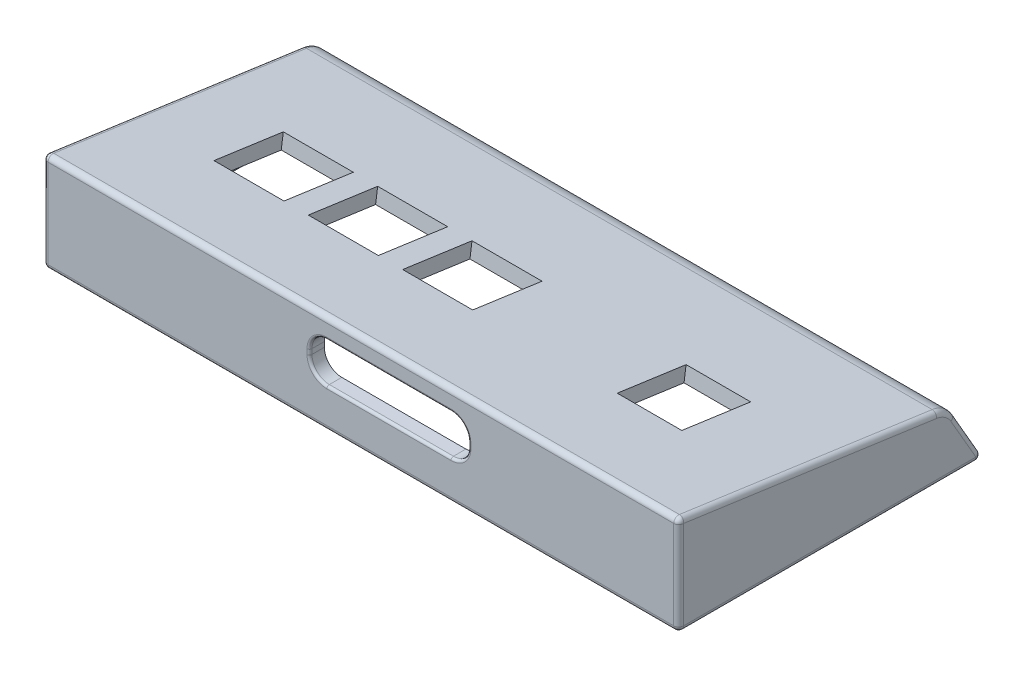
SolidWorks part; units mm, degrees
ref_plane "前视基准面" through (0, 0, 0) normal (0, 0, 1) x (1, 0, 0)
ref_plane "上视基准面" through (0, 0, 0) normal (0, 1, 0) x (1, 0, 0)
ref_plane "右视基准面" through (0, 0, 0) normal (1, 0, 0) x (0, 0, -1)
other "Configuration Table"
sketch "草图1" plane through (0, 0, 0) normal (1, 0, 0) x (0, 0, -1)
  line L0 (0, 0) -> (3, 0)
  line L1 (61.5924, 0) -> (54.4647, 12.3455)
  line L2 (54.4647, 12.3455) -> (0, 20)
  line L3 (0, 20) -> (0, 0)
  line L5 (58.1283, 0) -> (52.5983, 9.5783)
  line L6 (52.5983, 9.5783) -> (3, 16.5489)
  line L7 (3, 16.5489) -> (3, 0)
  line L8 (3, 16.5489) -> (3, 3) construction
  line L9 (56.3963, 3) -> (52.5983, 9.5783) construction
  line L10 (58.1283, 0) -> (61.5924, 0)
  line L11 (0, 0) -> (61.5924, 0) construction
  line L12 (3, 3) -> (56.3963, 3) construction
  dimension "D1" = 55
  dimension "D2" = 3
  dimension "D3" = 20
extrude "凸台-拉伸1" add sketch "草图1" along normal blind 125
sketch "草图2" plane through (0, 19.6126, -2.7564) normal (0, 0.9903, -0.1392) x (1, 0, 0)
  line L1 (97.149, 29.8765) -> (110.149, 29.8765)
  line L2 (97.149, 29.8765) -> (97.149, 15.8765)
  line L3 (97.149, 15.8765) -> (110.149, 15.8765)
  line L4 (110.149, 29.8765) -> (110.149, 15.8765)
  line L5 (53.988, 29.9265) -> (68.088, 29.9265)
  line L6 (53.988, 29.9265) -> (53.988, 15.8265)
  line L7 (53.988, 15.8265) -> (68.088, 15.8265)
  line L8 (68.088, 29.9265) -> (68.088, 15.8265)
  line L18 (62.5, 41.0069) -> (62.5, -31.3643) construction
  line L19 (125, 52.2165) -> (125, -2.7835) construction
  line L20 (34.988, 29.9265) -> (49.088, 29.9265)
  line L21 (34.988, 29.9265) -> (34.988, 15.8265)
  line L22 (34.988, 15.8265) -> (49.088, 15.8265)
  line L23 (49.088, 29.9265) -> (49.088, 15.8265)
  line L24 (15.988, 29.9265) -> (30.088, 29.9265)
  line L25 (15.988, 29.9265) -> (15.988, 15.8265)
  line L26 (15.988, 15.8265) -> (30.088, 15.8265)
  line L27 (30.088, 29.9265) -> (30.088, 15.8265)
  line L31 (-5.112, 22.8765) -> (145.7545, 22.8765) construction
  line L32 (125, -2.7835) -> (0, -2.7835) construction
  dimension "D1" = 13
  dimension "D2" = 14
  dimension "D3" = 14.1
  dimension "D4" = 14.1
  dimension "D5" = 7.05
  dimension "D7" = 62.5
  dimension "D8" = 7
  dimension "D9" = 34.649
  dimension "D10" = 3
  dimension "D6" = 8.512
  dimension "D11" = 25.66
extrude "切除-拉伸1" cut sketch "草图2" against normal blind 5
sketch "草图4" plane through (0, 0, 0) normal (0, 0, 1) x (1, 0, 0)
  line L0 (125, 20) -> (0, 20) construction
  line L1 (53.649, 15.9) -> (85.649, 15.9)
  line L2 (53.649, 15.9) -> (53.649, 7.9)
  line L3 (53.649, 7.9) -> (85.649, 7.9)
  line L4 (85.649, 15.9) -> (85.649, 7.9)
  line L5 (62.5, 49.94) -> (62.5, 4.3344) construction
  dimension "D1" = 4.1
  dimension "D2" = 23.149
  dimension "D3" = 8.851
  dimension "D4" = 8
extrude "切除-拉伸2" cut sketch "草图4" against normal blind 3
fillet "圆角2" radius 3.5 4 edges at (53.649, 7.9, -1.5) (53.649, 15.9, -1.5) (85.649, 7.9, -1.5) (85.649, 15.9, -1.5)
sketch "草图5" plane through (0, 0, 0) normal (-1, 0, 0) x (0, 0, 1)
  line L0 (-58.1283, 0) -> (-3, 0)
  line L8 (0, 0) -> (0, 20)
  line L9 (0, 20) -> (-54.4647, 12.3455)
  line L10 (-54.4647, 12.3455) -> (-61.5924, 0)
  line L11 (-61.5924, 0) -> (-58.1283, 0)
  line L12 (-58.1283, 0) -> (-52.5983, 9.5783)
  line L13 (-52.5983, 9.5783) -> (-3, 16.5489)
  line L14 (-3, 16.5489) -> (-3, 0)
  line L15 (-3, 0) -> (0, 0)
  line L16 (0, 0) -> (0, 20)
  line L17 (0, 20) -> (-54.4647, 12.3455)
  line L18 (-54.4647, 12.3455) -> (-61.5924, 0)
  line L19 (-61.5924, 0) -> (-58.1283, 0)
  line L23 (-3, 0) -> (0, 0)
  dimension "D1" = 0
extrude "凸台-拉伸2" add sketch "草图5" against normal blind 3
sketch "草图6" plane through (125, 0, 0) normal (1, 0, 0) x (0, 0, -1)
  line L0 (3, 0) -> (58.1283, 0)
  line L8 (0, 20) -> (0, 0)
  line L9 (0, 0) -> (3, 0)
  line L10 (3, 0) -> (3, 16.5489)
  line L11 (3, 16.5489) -> (52.5983, 9.5783)
  line L12 (52.5983, 9.5783) -> (58.1283, 0)
  line L13 (58.1283, 0) -> (61.5924, 0)
  line L14 (61.5924, 0) -> (54.4647, 12.3455)
  line L15 (54.4647, 12.3455) -> (0, 20)
  line L16 (0, 20) -> (0, 0)
  line L17 (0, 0) -> (3, 0)
  line L21 (58.1283, 0) -> (61.5924, 0)
  line L22 (61.5924, 0) -> (54.4647, 12.3455)
  line L23 (54.4647, 12.3455) -> (0, 20)
  dimension "D1" = 0
extrude "凸台-拉伸3" add sketch "草图6" along normal blind 3
fillet "圆角5" radius 5 1 edges at (64, 12.3455, -54.4647)
fillet "圆角6" radius 1 6 edges at (0, 11.8787, -54.1499) (128, 11.8787, -54.1499) (128, 16.3424, -26.0249) (0, 16.3424, -26.0249) (0, 5.1168, -58.6382) (128, 5.1168, -58.6382)
fillet "圆角8" radius 1 5 edges at (128, 0, -30.2189) (127.7071, 0, -61.2542) (0, 0, -30.2189) (0.2929, 0, -61.2542) (64, 0, -61.5924)
fillet "圆角9" radius 1 8 edges at (127.7071, 0.2929, 0) (128, 9.9951, 0) (127.7071, 19.7042, 0) (64, 20, 0) (0.2929, 19.7042, 0) (0, 9.9951, 0) (0.2929, 0.2929, 0) (64, 0, 0)
fillet "圆角10" radius 0.5 8 edges at (54.6741, 8.9251, 0) (53.649, 11.9, 0) (54.6741, 14.8749, 0) (69.649, 7.9, 0) (84.6239, 8.9251, 0) (85.649, 11.9, 0) (84.6239, 14.8749, 0) (69.649, 15.9, 0)
fillet "圆角11" radius 1 4 edges at (125, 0, -30.5642) (64, 0, -58.1283) (64, 0, -3) (3, 0, -30.5642)
